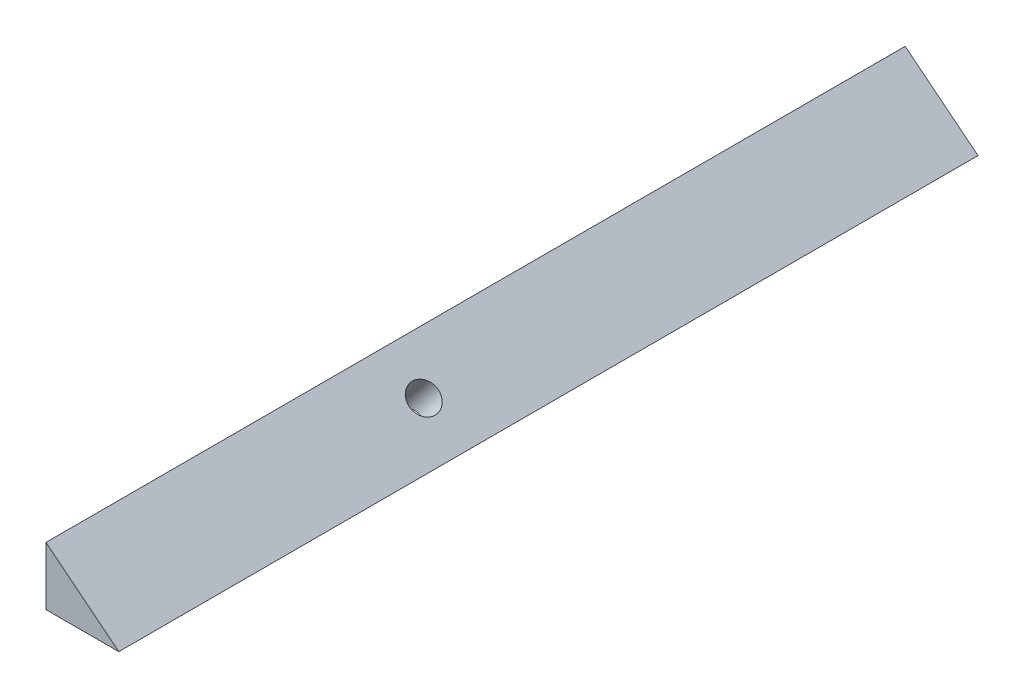
SolidWorks part; units mm, degrees
ref_plane "Front Plane" through (0, 0, 0) normal (0, 0, 1) x (1, 0, 0)
ref_plane "Top Plane" through (0, 0, 0) normal (0, 1, 0) x (1, 0, 0)
ref_plane "Right Plane" through (0, 0, 0) normal (1, 0, 0) x (0, 0, -1)
sketch "Sketch1" plane through (0, 0, 0) normal (0, 0, 1) x (1, 0, 0)
  line L0 (63.5, 0) -> (0, 50.8)
  line L1 (0, 0) -> (63.5, 0)
  line L2 (0, 0) -> (0, 50.8)
  line L3 (0, 50.8) -> (63.5, 50.8)
  line L4 (63.5, 0) -> (63.5, 50.8)
  dimension "D1" = 50.8
  dimension "D2" = 63.5
extrude "Boss-Extrude1" add sketch "Sketch1" against normal blind 38.1 contours L2 L1 L0 region at (21.1667, 16.9333, 0)
sketch "Sketch2" plane through (24.7805, 30.9756, 0) normal (0.6247, 0.7809, 0) x (0.7809, -0.6247, 0)
  line L0 (49.5852, 0) -> (-31.7345, 0) construction
  circle A0 centre (7.9717, 19.05) radius 12.7
  dimension "D1" = 25.4
  dimension "D2" = 19.05
extrude "Cut-Extrude1" cut sketch "Sketch2" against normal through all
sketch "Sketch3" plane through (0, 0, 0) normal (0, 0, 1) x (1, 0, 0)
  line L0 (0, 50.8) -> (0, 0)
  line L1 (0, 0) -> (63.5, 0)
  line L2 (63.5, 0) -> (0, 50.8)
extrude "Boss-Extrude2" add sketch "Sketch3" along normal blind 279.4
sketch "Sketch4" plane through (0, 0, -38.1) normal (0, 0, -1) x (-1, 0, 0)
  line L0 (0, 50.8) -> (-63.5, 0)
  line L1 (-63.5, 0) -> (0, 0)
  line L2 (0, 0) -> (0, 50.8)
extrude "Boss-Extrude3" add sketch "Sketch4" along normal blind 431.8
